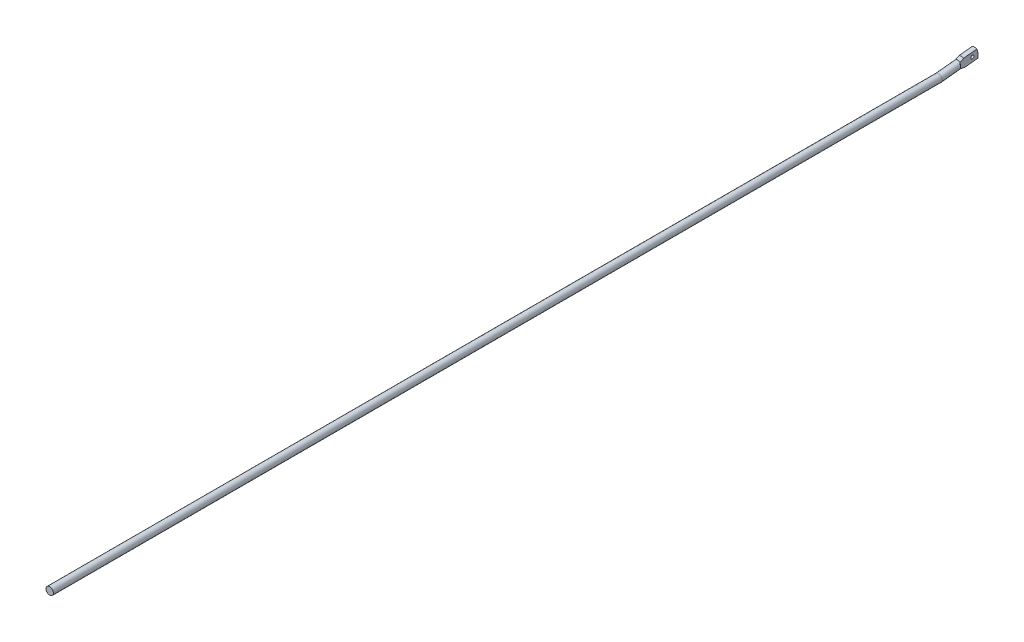
SolidWorks part; units mm, degrees
material "1023 Carbon Steel Sheet (SS)"
ref_plane "Front Plane" through (0, 0, 0) normal (0, 0, 1) x (1, 0, 0)
ref_plane "Top Plane" through (0, 0, 0) normal (0, 1, 0) x (1, 0, 0)
ref_plane "Right Plane" through (0, 0, 0) normal (1, 0, 0) x (0, 0, -1)
sketch "Sketch4" plane through (0, 0, 0) normal (1, 0, 0) x (0, 0, -1)
  line L0 (0, 0) -> (1000, 0) construction
  line L1 (0, 0) -> (960, 0)
  line L2 (960, 0) -> (1000, 4.2042)
  dimension "D1" = 1000
  dimension "D2" = 960
  dimension "D3" = 6
sketch "Sketch5" plane through (0, 0, 0) normal (0, 0, 1) x (1, 0, 0)
  circle A0 centre (0, 0) radius 4
  dimension "D1" = 8
sweep "Sweep1" add profiles "Sketch5" path "Sketch4"
sketch "Sketch6" plane through (0, 104.0018, -989.5108) normal (0, 0.1045, -0.9945) x (-1, 0, 0)
  line L2 (-2.5, -100.3473) -> (-2.5, -94.9185)
  line L3 (-2.5, -94.9185) -> (2.5, -94.9185)
  line L4 (2.5, -94.9185) -> (2.5, -104.7457)
  line L5 (2.5, -104.7457) -> (-2.5, -104.7457)
  line L6 (-2.5, -104.7457) -> (-2.5, -100.3473)
  point P10 (0, -100.3473)
extrude "Cut-Extrude2" cut sketch "Sketch6" against normal blind 19 flip side to cut
sketch "Sketch7" plane through (0, 104.0018, -989.5108) normal (0, 0.1045, -0.9945) x (-1, 0, 0)
  line L2 (-2.5, -97.2248) -> (-2.5, -103.4698)
  line L3 (2.5, -103.4698) -> (2.5, -97.2248)
  line L4 (-2.5, -97.2248) -> (-2.5, -103.4698)
  line L5 (2.5, -103.4698) -> (2.5, -97.2248)
  line L6 (-2.5, -103.4698) -> (-2.5, -104.9639)
  line L8 (2.5, -103.4698) -> (2.5, -104.9639)
  line L9 (-2.5, -97.2248) -> (-2.5, -95.7308)
  line L11 (2.5, -97.2248) -> (2.5, -95.7308)
  line L13 (-3.75, -96.6731) -> (-3.75, -104.0216) construction
  line L14 (3.75, -104.0216) -> (3.75, -96.6731) construction
  arc A0 (-2.5, -104.9639) -> (2.5, -104.9639) centre (0, -100.3473) ccw
  arc A1 (2.5, -95.7308) -> (-2.5, -95.7308) centre (0, -100.3473) ccw
  arc A2 (-2.5, -103.4698) -> (2.5, -103.4698) centre (0, -100.3473) ccw
  arc A3 (2.5, -97.2248) -> (-2.5, -97.2248) centre (0, -100.3473) ccw
  arc A6 (2.5, -97.2248) -> (-2.5, -97.2248) centre (0, -100.3473) ccw construction
  arc A7 (-2.5, -103.4698) -> (2.5, -103.4698) centre (0, -100.3473) ccw construction
  arc A8 (3.75, -96.6731) -> (-3.75, -96.6731) centre (0, -100.3473) ccw construction
  arc A9 (-3.75, -104.0216) -> (3.75, -104.0216) centre (0, -100.3473) ccw construction
  dimension "D1" = 0
  dimension "D2" = 1.25
extrude "Boss-Extrude2" add sketch "Sketch7" against normal blind 19
sketch "Sketch8" plane through (-2.5, 0, 0) normal (-1, 0, 0) x (0, 0, 1)
  line L5 (-980.7777, 5.3235) -> (-981.4305, -0.8873) construction
  line L8 (-999.8131, -1.0944) -> (-1000.1398, -2.7828)
  line L9 (-1000.1398, -2.7828) -> (-1007.1221, 2.7322)
  line L10 (-1007.1221, 2.7322) -> (-999.9764, 14.3187)
  line L11 (-999.9764, 14.3187) -> (-998.7155, 9.3481)
  arc A0 (-998.7155, 9.3481) -> (-999.8131, -1.0944) centre (-981.1041, 2.2181) ccw
extrude "Cut-Extrude6" cut sketch "Sketch8" against normal blind 10
ref_plane "Plane1" through (0, -105.0189, -11.0379) normal (0, -0.9945, -0.1045) x (-1, 0, 0)
sketch "Sketch9" plane through (0, -105.0189, -11.0379) normal (0, -0.9945, -0.1045) x (-1, 0, 0)
  line L0 (2.5, 975.9614) -> (2.5, 974.4614) construction
  line L1 (2.5, 975.9614) -> (4, 974.4614)
  line L2 (4, 954.741) -> (4, 975.9614) construction
  line L3 (4, 974.4614) -> (-4, 974.4614) construction
  line L4 (-4, 975.9614) -> (-4, 954.741) construction
  line L5 (4, 974.4614) -> (4.986, 974.4614)
  line L6 (4.986, 974.4614) -> (4.986, 997.5745)
  line L7 (4.986, 997.5745) -> (-6.2295, 997.5745)
  line L8 (-6.2295, 997.5745) -> (-6.2295, 974.4614)
  line L9 (-6.2295, 974.4614) -> (-4, 974.4614)
  line L10 (-4, 974.4614) -> (-2.5, 975.9614)
  line L11 (-2.5, 975.9614) -> (-2.5, 995.9407)
  line L12 (-2.5, 995.9407) -> (2.5, 995.9407)
  line L13 (2.5, 995.9407) -> (2.5, 975.9614)
  dimension "D1" = 1.5
extrude "Cut-Extrude4" cut sketch "Sketch9" against normal blind 19
chamfer "Chamfer4" distance 1.25 distance2 4 2 edges at (0, 7.4394, -980.5553) (0, -3.0031, -981.6529) first distance on face at (0, 6.4421, -980.6601) first distance on face at (0, -2.0059, -981.548)
sketch "Sketch10" plane through (2.5, 0, 0) normal (1, 0, 0) x (0, 0, -1)
  line L0 (981.1041, 2.2181) -> (1000, 4.2042) construction
  line L1 (980.7777, 5.3235) -> (981.4305, -0.8873) construction
  line L2 (994.0329, 3.577) -> (993.6704, 7.0254) construction
  arc A0 (999.9163, -0.4466) -> (998.9512, 8.7359) centre (981.1041, 2.2181) ccw construction
  circle A1 centre (994.0329, 3.577) radius 1.75
  dimension "D3" = 3.5
  dimension "D1" = 90
  dimension "D2" = 6
extrude "Cut-Extrude7" cut sketch "Sketch10" against normal up to surface (5 mm away) up to face at (-2.5, 2.762, -988.6604)
